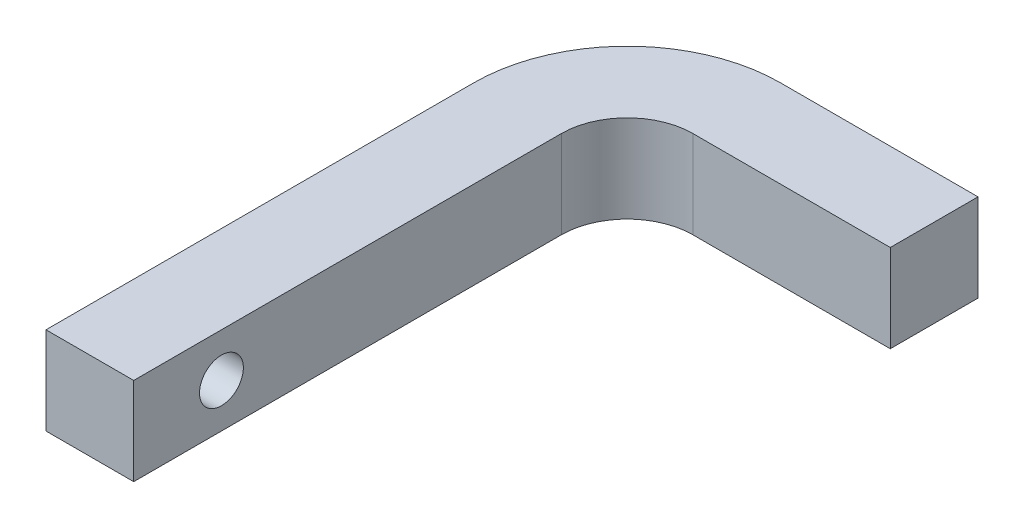
SolidWorks part; units mm, degrees
ref_plane "Front Plane" through (0, 0, 0) normal (0, 0, 1) x (1, 0, 0)
ref_plane "Top Plane" through (0, 0, 0) normal (0, 1, 0) x (1, 0, 0)
ref_plane "Right Plane" through (0, 0, 0) normal (1, 0, 0) x (0, 0, -1)
ref_axis "Z" through (0, 0, -2.65) along (0, 0, 1)
sketch "Sketch1" plane through (0, 0, 0) normal (0, 1, 0) x (1, 0, 0)
  line L0 (-9, 0) -> (9, 0)
  line L1 (-23, -14) -> (-23, -53)
  line L2 (-23, -53) -> (-15, -53)
  line L3 (-15, -53) -> (-15, -14)
  line L4 (-9, -8) -> (9, -8)
  line L5 (0, -8) -> (0, 0) construction
  line L6 (15, -53) -> (15, -14) construction
  line L7 (23, -53) -> (15, -53) construction
  line L8 (23, -14) -> (23, -53) construction
  line L9 (9, 0) -> (9, -8)
  arc A0 (-9, 0) -> (-23, -14) centre (-9, -14) ccw
  arc A1 (-15, -14) -> (-9, -8) centre (-9, -14) cw
  arc A2 (15, -14) -> (9, -8) centre (9, -14) ccw construction
  arc A3 (9, 0) -> (23, -14) centre (9, -14) cw construction
  dimension "D3" = 6
  dimension "D1" = 30
  dimension "D2" = 8
  dimension "D4" = 45
extrude "Boss-Extrude1" add sketch "Sketch1" along normal blind 4 and the other way blind 4
sketch "Sketch2" plane through (-15, 0, 0) normal (-1, 0, 0) x (0, 0, 1)
  line L1 (17.6, 0) -> (-17.6, 0) construction
  line L2 (0, -4.4) -> (0, 4.4) construction
  circle A0 centre (45, 0) radius 2
  dimension "D1" = 4
  dimension "D2" = 45
extrude "Cut-Extrude1" cut sketch "Sketch2" against normal through all both and the other way through all
ref_axis "Axis2" through (-56.6767, 0, 45) along (1, 0, 0)
equation "\"width\"= \"EyeDiameter\" + \"EyeClearance\""
equation "\"prongwidth\"= 8"
equation "\"D2@Sketch1\"=\"prongwidth\""
equation "\"D3@Sketch1\"=\"width\"/5"
equation "\"pronglength\"= \"BasePlaneDistance\"'model implicitly adds clearance (of prongwidth) to the hole drilled at the baseplanedistance"
equation "\"D4@Sketch1\"=\"pronglength\""
equation "\"D1@Boss-Extrude1\"=\"prongwidth\"/2"
equation "\"D2@Boss-Extrude1\"=\"prongwidth\"/2"
equation "\"lbracket-plane-to-axis\"= \"BasePlaneDistance\""
equation "\"D2@Sketch2\"=\"lbracket-plane-to-axis\""
equation "\"EyeDiameter\" = 28"
equation "\"BasePlaneDistance\" = 45"
equation "\"EyeClearance\" = 2"
